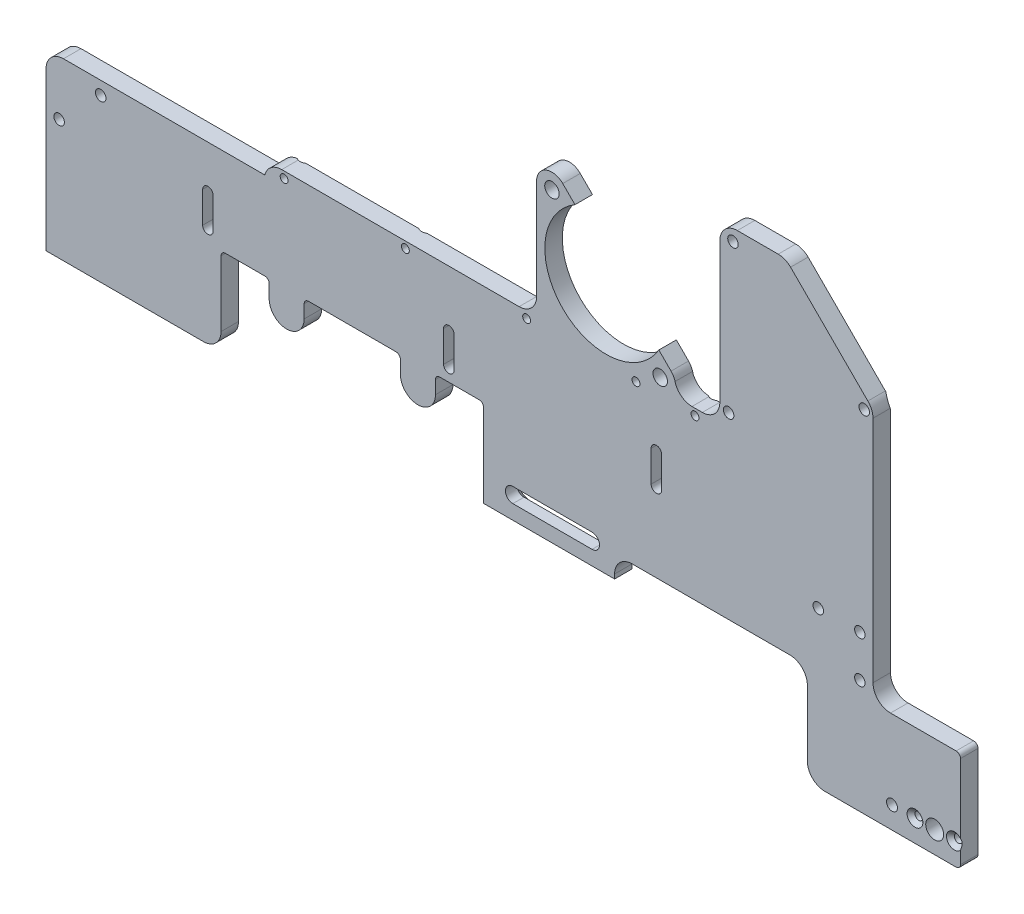
SolidWorks part; units mm, degrees
material "3.1355 (EN-AW 2024)"
ref_plane "Спереди" through (0, 0, 0) normal (0, 0, 1) x (1, 0, 0)
ref_plane "Сверху" through (0, 0, 0) normal (0, 1, 0) x (1, 0, 0)
ref_plane "Справа" through (0, 0, 0) normal (1, 0, 0) x (0, 0, -1)
sketch "Model" plane through (0, 0, 0) normal (0, 0, 1) x (1, 0, 0)
  line L1 (122.3431, 31.8431) -> (128, 37.5) construction
  line L3 (112.1256, 49.8744) -> (112.1256, 23)
  line L11 (154, 23) -> (154, 0)
  line L19 (0, 0) -> (0, 20)
  line L39 (0, 20) -> (50, 20)
  line L44 (112.1256, 23) -> (50, 23)
  line L49 (50, 23) -> (50, 20)
  line L54 (0, 0) -> (0, -20)
  line L55 (0, -20) -> (40, -20)
  line L56 (40, -20) -> (40, 0)
  line L57 (40, 0) -> (154, 0)
  line L60 (143.8744, 25.1256) -> (143.8744, 23)
  line L62 (143.8744, 23) -> (154, 23)
  line L65 (142.8492, 27.6005) -> (140.06, 30.3897)
  line L69 (120.8897, 49.56) -> (118.1005, 52.3492)
  line L71 (128, 37.5) -> (140.3744, 25.1256) construction
  line L72 (128, 37.5) -> (115.6256, 49.8744) construction
  circle A10 centre (140.3744, 25.1256) radius 1
  circle A12 centre (115.6256, 49.8744) radius 1
  arc A14 (143.8744, 25.1256) -> (142.8492, 27.6005) centre (140.3744, 25.1256) ccw
  arc A44 (118.1005, 52.3492) -> (112.1256, 49.8744) centre (115.6256, 49.8744) ccw
  arc A46 (120.8897, 49.56) -> (140.06, 30.3897) centre (128, 37.5) ccw
  circle A47 centre (122.3431, 31.8431) radius 2.5 construction
  dimension "D3" = 5
  dimension "D8" = 128
  dimension "D11" = 37.5
  dimension "D15" = 20
  dimension "D26" = 2
  dimension "D27" = 3.5
  dimension "D4" = 28
  dimension "D12" = 45
  dimension "D5" = 20
  dimension "D6" = 8
  dimension "D7" = 50
  dimension "D10" = 35
  dimension "D13" = 23
  dimension "D18" = 154
  dimension "D22" = 40
extrude "База" add sketch "Model" against normal blind 4
sketch "Эскиз15" plane through (0, 0, -4) normal (0, 0, 1) x (1, 0, 0)
  line L0 (40, 0) -> (154, 0) construction
  line L1 (51, 0) -> (59, 0)
  line L2 (51, 0) -> (51, -8)
  line L3 (51, -8) -> (59, -8)
  line L4 (59, 0) -> (59, -8)
  line L6 (81, 0) -> (89, 0)
  line L7 (81, 0) -> (81, -8)
  line L8 (81, -8) -> (89, -8)
  line L9 (89, 0) -> (89, -8)
  point P10 (55, -8)
  point P12 (85, -8)
  dimension "D1" = 8
  dimension "D2" = 55
  dimension "D3" = 30
extrude "Вставка в профиль 30*60" add sketch "Эскиз15" along normal up to surface (4 mm away) up to face at (116.6256, 49.8744, 0)
hole_wizard "Крепление двигателя M4" positions "Эскиз3" profile "Эскиз4" tap size "M4" standard "DIN" end condition through all
sketch "Эскиз3" plane through (0, 0, 0) normal (0, 0, 1) x (1, 0, 0)
  point P0 (115.6256, 49.8744)
  point P3 (140.3744, 25.1256)
sketch "Эскиз4" plane through (115.6256, 49.8744, 0) normal (1, 0, 0) x (0, -1, 0)
  line L0 (0, 0) -> (0, 4)
  line L1 (0, 4) -> (1.65, 4)
  line L2 (1.65, 4) -> (1.65, 0)
  line L5 (1.65, 0) -> (0, 0)
  line L11 (0, -6.35) -> (0, 107.95) construction
  dimension "Диаметр проходного сверла" = 3.3
  dimension "Глубина проходного сверла" = 4
cosmetic thread "Отверстие резьбы1" parameters "D2"=4
cosmetic thread "Отверстие резьбы2" parameters "D2"=4
hole_wizard "Регулировка уровня M2" positions "Эскиз5" profile "Эскиз6" size "M2" standard "DIN" slot yes end condition through all
sketch "Эскиз5" plane through (0, 0, -4) normal (0, 0, 1) x (1, 0, 0)
  line L0 (37, 1.75) -> (37, 11.25) construction
  line L4 (40, 0) -> (51, 0) construction
  point P0 (37, 6.5)
  point P4 (139.5, 6.5)
  point P20 (92.07, 6.5)
  dimension "D1" = 9.5
  dimension "D2" = 102.5
  dimension "D3" = 6.5
  dimension "D4" = 37
  dimension "D5" = 55.07
sketch "Эскиз6" plane through (37, 6.5, -4) normal (1, 0, 0) x (0, 1, 0)
  line L0 (0, 0) -> (0, 4)
  line L1 (0, 4) -> (1.2, 4)
  line L2 (1.2, 4) -> (1.2, 1)
  line L3 (1.2, 1) -> (2.2, 0)
  line L5 (2.2, 0) -> (0, 0)
  line L6 (-1.2, 1) -> (-2.2, 0) construction
  line L11 (0, -6.35) -> (0, 107.95) construction
  dimension "Диаметр сквозного отверстия" = 2.4
  dimension "Глубина сквозного отверстия" = 4
  dimension "Диаметр передней зенковки" = 4.4
  dimension "Угол передней зенковки" = 90
sketch "Эскиз7" plane through (0, 0, -4) normal (0, 0, 1) x (1, 0, 0)
  line L0 (154, 23) -> (154, 63)
  line L1 (154, 63) -> (169, 63)
  line L2 (169, 63) -> (189, 43)
  line L3 (189, 43) -> (189, -15)
  line L5 (100, -20) -> (100, 0)
  line L6 (40, 0) -> (51, 0) construction
  line L8 (154, 0) -> (154, 23) construction
  line L9 (100, 0) -> (154, 0)
  line L10 (154, 0) -> (154, 23)
  line L11 (189, -15) -> (129.95, -15)
  line L12 (129.95, -15) -> (129.95, -20)
  line L13 (129.95, -20) -> (100, -20)
  line L14 (0, 20) -> (0, -20) construction
  dimension "D1" = 40
  dimension "D2" = 15
  dimension "D3" = 135
  dimension "D4" = 20
  dimension "D5" = 35
  dimension "D6" = 29.95
  dimension "D7" = 5
  dimension "D8" = 100
extrude "Панель управления" add sketch "Эскиз7" along normal up to surface (4 mm away) up to face at (37, 6.5, 0)
fillet "Скругление5" radius 1 6 edges at (89, 0, -2) (81, 0, -2) (59, 0, -2) (51, 0, -2) (100, 0, -2) (40, 0, -2)
hole_wizard "Крепление M2" positions "Эскиз10" profile "Эскиз11" countersink size "M2" standard "DIN" end condition through all
sketch "Эскиз10" plane through (0, 0, -4) normal (0, 0, -1) x (-1, 0, 0)
  point P0 (-3, 7.5)
  point P3 (-12.5, 17)
  point P30 (-186, -2.5)
  point P33 (-186, -12)
  point P36 (-176.5, -2.5)
  point P64 (-156, 25.95)
  point P67 (-157, 60.32)
  point P68 (-187, 42.08)
  dimension "D1" = 3
  dimension "D2" = 12.5
  dimension "D3" = 7.5
  dimension "D4" = 17
sketch "Эскиз11" plane through (3, 7.5, -4) normal (1, 0, 0) x (0, 1, 0)
  line L0 (0, 0) -> (0, 4)
  line L1 (0, 4) -> (1.2, 4)
  line L2 (1.2, 4) -> (1.2, 1)
  line L3 (1.2, 1) -> (2.2, 0)
  line L5 (2.2, 0) -> (0, 0)
  line L6 (-1.2, 1) -> (-2.2, 0) construction
  line L11 (0, -6.35) -> (0, 107.95) construction
  dimension "Диаметр сквозного отверстия" = 2.4
  dimension "Глубина сквозного отверстия" = 4
  dimension "Диаметр передней зенковки" = 4.4
  dimension "Угол передней зенковки" = 90
hole_wizard "Прорезь стопора M3" positions "Эскиз13" profile "Эскиз14" size "M3" standard "DIN" slot yes end condition through all
sketch "Эскиз13" plane through (0, 0, -4) normal (0, 0, -1) x (-1, 0, 0)
  line L0 (-105, -15) -> (-126.5, -15) construction
  line L10 (-100, -1) -> (-100, -20) construction
  point P0 (-115.75, -15)
  dimension "D1" = 5
  dimension "D2" = 21.5
  dimension "D4" = 15
sketch "Эскиз14" plane through (115.75, -15, -4) normal (1, 0, 0) x (0, 1, 0)
  line L0 (0, 0) -> (0, 4)
  line L1 (0, 4) -> (1.7, 4)
  line L2 (1.7, 4) -> (1.7, 1.45)
  line L3 (1.7, 1.45) -> (3.15, 0)
  line L5 (3.15, 0) -> (0, 0)
  line L6 (-1.7, 1.45) -> (-3.15, 0) construction
  line L11 (0, -6.35) -> (0, 107.95) construction
  dimension "Диаметр сквозного отверстия" = 3.4
  dimension "Глубина сквозного отверстия" = 4
  dimension "Диаметр передней зенковки" = 6.3
  dimension "Угол передней зенковки" = 90
hole_wizard "Зенковка для винта M1.6" positions "Эскиз16" profile "Эскиз17" countersink size "M1.6" standard "DIN" end condition through all
sketch "Эскиз16" plane through (0, 0, -4) normal (0, 0, -1) x (-1, 0, 0)
  line L0 (-50, 20) -> (0, 20) construction
  point P0 (-148.32, 21.5)
  point P3 (-134.84, 21.5)
  point P6 (-109.84, 21.5)
  point P9 (-82.13, 21.5)
  point P12 (-54.42, 21.5)
  dimension "D1" = 1.5
  dimension "D2" = 54.42
  dimension "D3" = 27.71
  dimension "D4" = 27.71
  dimension "D5" = 25
  dimension "D6" = 13.48
sketch "Эскиз17" plane through (148.32, 21.5, -4) normal (1, 0, 0) x (0, 1, 0)
  line L0 (0, 0) -> (0, 4)
  line L1 (0, 4) -> (0.9, 4)
  line L2 (0.9, 4) -> (0.9, 0.9)
  line L3 (0.9, 0.9) -> (1.8, 0)
  line L5 (1.8, 0) -> (0, 0)
  line L6 (-0.9, 0.9) -> (-1.8, 0) construction
  line L11 (0, -6.35) -> (0, 107.95) construction
  dimension "Диаметр сквозного отверстия" = 1.8
  dimension "Глубина сквозного отверстия" = 4
  dimension "Диаметр передней зенковки" = 3.6
  dimension "Угол передней зенковки" = 90
sketch "Эскиз18" plane through (0, 0, -4) normal (0, 0, -1) x (-1, 0, 0)
  line L0 (-129.95, -15) -> (-189, -15) construction
  line L1 (-174, -15) -> (-209, -15)
  line L2 (-174, -15) -> (-174, -38)
  line L3 (-174, -38) -> (-209, -38)
  line L4 (-209, -15) -> (-209, -38)
  line L5 (-189, -15) -> (-189, 43) construction
  dimension "D1" = 23
  dimension "D2" = 20
  dimension "D3" = 35
extrude "Бобышка-Вытянуть1" add sketch "Эскиз18" against normal up to surface (4 mm away) up to face at (147.42, 21.5, 0)
fillet "Скругление4" radius 4 17 edges at (0, 20, -2) (112.1256, 23, -2) (50, 23, -2) (143.8744, 23, -2) (154, 23, -2) (154, 63, -2) (189, 43, -2) (169, 63, -2) (129.95, -15, -2) (81, -8, -2) (89, -8, -2) (59, -8, -2) (51, -8, -2) (174, -15, -2) (174, -38, -2) (40, -20, -2) (189, -15, -2)
sketch "Эскиз19" plane through (0, 0, -4) normal (0, 0, -1) x (-1, 0, 0)
  circle A0 centre (-203.1, -33) radius 2.05
  dimension "D1" = 4.1
  dimension "D2" = 33
  dimension "D3" = 203.1
extrude "Вырез-Вытянуть1" cut sketch "Эскиз19" against normal up to surface (4 mm away) up to face at (147.42, 21.5, 0)
hole_wizard "Зенковка для винта с полупотайной головкой M1.61" positions "Эскиз20" profile "Эскиз21" countersink size "M1.6" standard "ISO" end condition through all
sketch "Эскиз20" plane through (0, 0, 0) normal (0, 0, 1) x (1, 0, 0)
  line L0 (207.6, -33) -> (203.1, -33) construction
  line L1 (203.1, -33) -> (198.6, -33) construction
  point P0 (207.6, -33)
  point P2 (198.6, -33)
  dimension "D1" = 9
sketch "Эскиз21" plane through (207.6, -33, 0) normal (1, 0, 0) x (0, -1, 0)
  line L0 (0, 0) -> (0, 4.2334)
  line L1 (0, 4.2334) -> (0.9, 4.2334)
  line L2 (0.9, 4.2334) -> (0.9, 0.9)
  line L3 (0.9, 0.9) -> (1.8, 0)
  line L5 (1.8, 0) -> (0, 0)
  line L6 (-0.9, 0.9) -> (-1.8, 0) construction
  line L11 (0, -6.35) -> (0, 107.95) construction
  dimension "Диаметр сквозного отверстия" = 1.8
  dimension "Глубина сквозного отверстия" = 4.2334
  dimension "Диаметр передней зенковки" = 3.6
  dimension "Угол передней зенковки" = 90
hole_wizard "Отверстие обработанное метчиком M31" positions "Эскиз22" profile "Эскиз23" tap size "M3" standard "DIN" end condition through all
sketch "Эскиз22" plane through (0, 0, 0) normal (0, 0, 1) x (1, 0, 0)
  circle A0 centre (203.1, -33) radius 2.05 construction
  point P0 (193.35, -33)
  dimension "D1" = 9.75
  dimension "D2" = 33
sketch "Эскиз23" plane through (193.35, -33, 0) normal (1, 0, 0) x (0, -1, 0)
  line L0 (0, 0) -> (0, 4.2334)
  line L1 (0, 4.2334) -> (1.25, 4.2334)
  line L2 (1.25, 4.2334) -> (1.25, 0)
  line L5 (1.25, 0) -> (0, 0)
  line L11 (0, -6.35) -> (0, 107.95) construction
  dimension "Диаметр проходного сверла" = 2.5
  dimension "Глубина проходного сверла" = 4.2334
cosmetic thread "Отверстие резьбы3" parameters "D2"=3
fillet "Скругление6" radius 1 2 edges at (209, -38, -2) (209, -15, -2)
